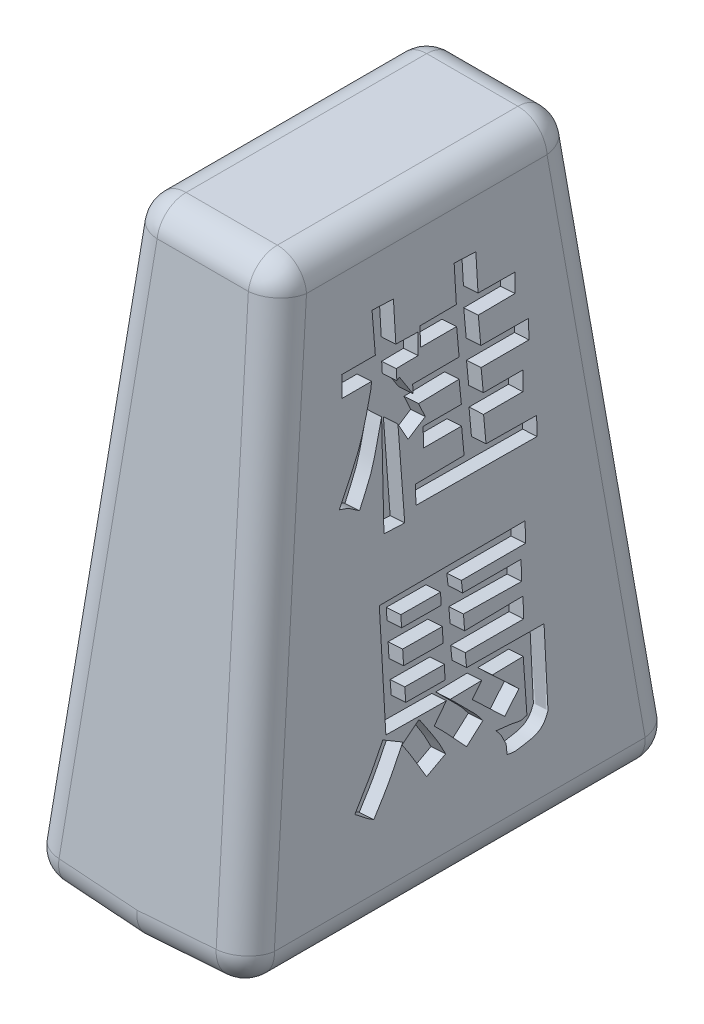
SolidWorks part; units mm, degrees
ref_plane "Płaszczyzna przednia" through (0, 0, 0) normal (0, 0, 1) x (1, 0, 0)
ref_plane "Płaszczyzna górna" through (0, 0, 0) normal (0, 1, 0) x (1, 0, 0)
ref_plane "Płaszczyzna prawa" through (0, 0, 0) normal (1, 0, 0) x (0, 0, -1)
sketch "Szkic1" plane through (0, 0, 0) normal (0, 0, 1) x (1, 0, 0)
  line L0 (0, 0) -> (0, 40)
  line L1 (3.1225, 40) -> (-3.1225, 40)
  line L2 (-5.1185, 38.1262) -> (-7.3738, 2.4704)
  line L3 (-5.504, 0.3481) -> (0, 0)
  line L4 (5.504, 0.3481) -> (0, 0)
  line L5 (5.1185, 38.1262) -> (7.3738, 2.4704)
  arc A0 (-3.1225, 40) -> (-5.1185, 38.1262) centre (-3.1225, 38) ccw
  arc A1 (-7.3738, 2.4704) -> (-5.504, 0.3481) centre (-5.3777, 2.3441) ccw
  arc A2 (7.3738, 2.4704) -> (5.504, 0.3481) centre (5.3777, 2.3441) cw
  arc A3 (3.1225, 40) -> (5.1185, 38.1262) centre (3.1225, 38) cw
  point P7 (-5, 40)
  point P10 (-7.5, 0.4744)
  point P17 (7.5, 0.4744)
  point P18 (5, 40)
  dimension "D5" = 2
  dimension "D1" = 40
  dimension "D2" = 90
  dimension "D3" = 5
  dimension "D4" = 7.5
extrude "Dodanie-wyciągnięcie1" add sketch "Szkic1" along normal blind 30 contours L2 A1 L3 L0 L1 A0 | A3 L1 L0 L4 A2 L5 region at (-3.1441, 18.7866, 0) region at (3.1441, 18.7866, 0)
ref_plane "Płaszczyzna1" through (5.1225, 0, 0) normal (1, 0, 0) x (0, 0, -1)
ref_plane "Płaszczyzna2" through (15.1225, 0, 0) normal (1, 0, 0) x (0, 0, -1)
sketch "Szkic7" plane through (15.1225, 0, 0) normal (1, 0, 0) x (0, 0, -1)
  line L0 (-25, 40) -> (-5, 40)
  line L1 (-30, 40) -> (0, 40) construction
  line L2 (-5, 40) -> (0, 0)
  line L3 (0, 0) -> (-30, 0)
  line L4 (-30, 0) -> (0, 0) construction
  line L5 (-15, 0) -> (-15, 40)
  line L6 (-25, 40) -> (-30, 0)
  line L8 (0, 0) -> (-30, 0)
  line L9 (0, 0) -> (0, 40)
  line L10 (0, 40) -> (-30, 40)
  line L11 (-30, 0) -> (-30, 40)
  dimension "D1" = 10
  dimension "D2" = 15
  dimension "D3" = 40
extrude "Wytnij-wyciągnięcie11" cut sketch "Szkic7" against normal through all and the other way through all contours L11 L6 L10 | L9 L10 L2 region at (15.1225, 26.6667, 28.3333) region at (15.1225, 26.6667, 1.6667)
fillet "Zaokrąglenie2" radius 2 18 edges at (0, 40, 5) (-4.4914, 39.4582, 4.9323) (-6.2461, 20.2983, 2.5373) (-6.8784, 1.022, 0.1278) (-2.752, 0.1741, 0.0218) (2.752, 0.1741, 0.0218) (6.8784, 1.022, 0.1278) (6.2461, 20.2983, 2.5373) (4.4914, 39.4582, 4.9323) (4.4914, 39.4582, 25.0677) (6.2461, 20.2983, 27.4627) (6.8784, 1.022, 29.8722) (2.752, 0.1741, 29.9782) (-2.752, 0.1741, 29.9782) (-6.8784, 1.022, 29.8722) (-6.2461, 20.2983, 27.4627) (-4.4914, 39.4582, 25.0677) (0, 40, 25)
sketch "Szkic8" plane through (7.5, 0.4744, 0) normal (0.998, 0.0631, 0) x (0, 0, -1)
  line L0 (341.3333, 1024) -> (1706.6667, 1024) construction
  line L1 (-18.9383, 34.682) -> (-17.4783, 34.622)
  line L2 (-17.4783, 34.622) -> (-17.4783, 32.022)
  line L3 (-17.4783, 32.022) -> (-15.9783, 31.982)
  line L4 (-15.9783, 31.982) -> (-16.0383, 30.662)
  line L5 (-16.0383, 30.662) -> (-17.5383, 30.642)
  line L6 (-17.5383, 30.642) -> (-17.5383, 29.942)
  line L7 (-17.5383, 29.942) -> (-17.3583, 30.062)
  line L8 (-17.3583, 30.062) -> (-16.5183, 28.702)
  line L9 (-16.5183, 28.702) -> (-16.4983, 29.242)
  line L10 (-16.4983, 29.242) -> (-13.3183, 29.262)
  line L11 (-13.3183, 29.262) -> (-13.3783, 31.042)
  line L12 (-13.3783, 31.042) -> (-15.8583, 31.042)
  line L13 (-15.8583, 31.042) -> (-15.7983, 32.262)
  line L14 (-15.7983, 32.262) -> (-13.3183, 32.282)
  line L15 (-13.3183, 32.282) -> (-13.3183, 34.662)
  line L16 (-13.3183, 34.662) -> (-11.8383, 34.602)
  line L17 (-11.8383, 34.602) -> (-11.8383, 32.222)
  line L18 (-11.8383, 32.222) -> (-9.3183, 32.202)
  line L19 (-9.3183, 32.202) -> (-9.3783, 31.002)
  line L20 (-9.3783, 31.002) -> (-11.8983, 30.982)
  line L21 (-11.8983, 30.982) -> (-11.8383, 29.202)
  line L22 (-11.8383, 29.202) -> (-8.5783, 29.182)
  line L23 (-8.5783, 29.182) -> (-8.6183, 27.962)
  line L24 (-8.6183, 27.962) -> (-11.8983, 27.962)
  line L25 (-11.8983, 27.962) -> (-11.8383, 26.482)
  line L26 (-11.8383, 26.482) -> (-9.1383, 26.482)
  line L27 (-9.1383, 26.482) -> (-9.1983, 25.262)
  line L28 (-9.1983, 25.262) -> (-11.8983, 25.262)
  line L29 (-11.8983, 25.262) -> (-11.8383, 23.542)
  line L30 (-11.8383, 23.542) -> (-8.3783, 23.502)
  line L31 (-8.3783, 23.502) -> (-8.4183, 22.302)
  line L32 (-8.4183, 22.302) -> (-16.7183, 22.362)
  line L33 (-16.7183, 22.362) -> (-16.6583, 23.562)
  line L34 (-16.6583, 23.562) -> (-13.3383, 23.602)
  line L35 (-13.3383, 23.602) -> (-13.3983, 25.322)
  line L36 (-13.3983, 25.322) -> (-15.9983, 25.322)
  line L37 (-15.9983, 25.322) -> (-15.9583, 26.542)
  line L38 (-15.9583, 26.542) -> (-13.3383, 26.542)
  line L39 (-13.3383, 26.542) -> (-13.3983, 28.022)
  line L40 (-13.3983, 28.022) -> (-16.1783, 27.962)
  line L41 (-16.1783, 27.962) -> (-15.7783, 27.022)
  line L42 (-15.7783, 27.022) -> (-16.9983, 26.302)
  line L43 (-16.9983, 26.302) -> (-17.6183, 27.482)
  line L44 (-17.6183, 27.482) -> (-17.5183, 21.742)
  line L45 (-17.5183, 21.742) -> (-18.9383, 21.802)
  line L46 (-18.9383, 21.802) -> (-18.6783, 28.422)
  line L47 (-19.2183, 30.722) -> (-21.2383, 30.722)
  line L48 (-21.2383, 30.722) -> (-21.1783, 32.062)
  line L49 (-21.1783, 32.062) -> (-18.8783, 32.062)
  line L50 (-18.8783, 32.062) -> (-18.9383, 34.682)
  line L51 (-9.5983, 18.002) -> (-9.5183, 17.962)
  line L52 (-9.5183, 17.962) -> (-9.5583, 16.702)
  line L53 (-9.5583, 16.702) -> (-13.9583, 16.702)
  line L54 (-13.9583, 16.702) -> (-13.9183, 15.962)
  line L55 (-13.9183, 15.962) -> (-9.9183, 15.962)
  line L56 (-9.9183, 15.962) -> (-9.9583, 14.702)
  line L57 (-9.9583, 14.702) -> (-13.9383, 14.762)
  line L58 (-13.9383, 14.762) -> (-13.9183, 13.782)
  line L59 (-13.9183, 13.782) -> (-9.9783, 13.842)
  line L60 (-9.9783, 13.842) -> (-9.9183, 13.802)
  line L61 (-9.9183, 13.802) -> (-9.9583, 12.542)
  line L62 (-9.9583, 12.542) -> (-13.9583, 12.542)
  line L63 (-13.9583, 12.542) -> (-13.9183, 11.662)
  line L64 (-13.9183, 11.662) -> (-8.6183, 11.622)
  line L65 (-10.0783, 7.062) -> (-10.1183, 10.462)
  line L66 (-10.1183, 10.462) -> (-12.2383, 10.422)
  line L67 (-12.2383, 10.422) -> (-10.5183, 8.802)
  line L68 (-10.5183, 8.802) -> (-11.5583, 7.702)
  line L69 (-11.5583, 7.702) -> (-13.6583, 9.702)
  line L70 (-13.6583, 9.702) -> (-12.9583, 10.462)
  line L71 (-12.9583, 10.462) -> (-15.1183, 10.422)
  line L72 (-13.0183, 8.182) -> (-14.1983, 7.242)
  line L73 (-16.2783, 9.442) -> (-15.3783, 10.462)
  line L74 (-15.3783, 10.462) -> (-19.5183, 10.502)
  line L75 (-19.5183, 10.502) -> (-19.4983, 17.942)
  line L76 (-19.4983, 17.942) -> (-9.5983, 17.982)
  line L77 (-9.5983, 17.982) -> (-9.5983, 18.002)
  line L78 (-18.0983, 16.742) -> (-15.3783, 16.722)
  line L79 (-15.3783, 16.722) -> (-15.3983, 15.962)
  line L80 (-15.3983, 15.962) -> (-18.0983, 15.982)
  line L81 (-18.0983, 15.982) -> (-18.0983, 16.742)
  line L82 (-18.0983, 14.762) -> (-15.3783, 14.742)
  line L83 (-15.3783, 14.742) -> (-15.3983, 13.782)
  line L84 (-15.3983, 13.782) -> (-18.0983, 13.802)
  line L85 (-18.0983, 13.802) -> (-18.0983, 14.762)
  line L86 (-18.0983, 12.582) -> (-15.3783, 12.562)
  line L87 (-15.3783, 12.562) -> (-15.3983, 11.662)
  line L88 (-15.3983, 11.662) -> (-18.0783, 11.682)
  line L89 (-18.0783, 11.682) -> (-18.0983, 12.582)
  line L90 (-15.6183, 7.522) -> (-16.9583, 6.862)
  line L91 (-18.4783, 9.422) -> (-17.2783, 10.282)
  line L92 (-19.7383, 10.322) -> (-18.4183, 9.562)
  line L93 (-9.5983, 18.002) -> (-9.5183, 17.962)
  line L94 (-9.5183, 17.962) -> (-9.5583, 16.702)
  line L95 (-9.5583, 16.702) -> (-13.9583, 16.702)
  line L96 (-13.9583, 16.702) -> (-13.9183, 15.962)
  line L97 (-13.9183, 15.962) -> (-9.9183, 15.962)
  line L98 (-9.9183, 15.962) -> (-9.9583, 14.702)
  line L99 (-9.9583, 14.702) -> (-13.9383, 14.762)
  line L100 (-13.9383, 14.762) -> (-13.9183, 13.782)
  line L101 (-13.9183, 13.782) -> (-9.9783, 13.842)
  line L102 (-9.9783, 13.842) -> (-9.9183, 13.802)
  line L103 (-9.9183, 13.802) -> (-9.9583, 12.542)
  line L104 (-9.9583, 12.542) -> (-13.9583, 12.542)
  line L105 (-13.9583, 12.542) -> (-13.9183, 11.662)
  line L106 (-13.9183, 11.662) -> (-8.6183, 11.622)
  line L107 (-10.0783, 7.062) -> (-10.1183, 10.462)
  line L108 (-10.1183, 10.462) -> (-12.2383, 10.422)
  line L109 (-12.2383, 10.422) -> (-10.5183, 8.802)
  line L110 (-10.5183, 8.802) -> (-11.5583, 7.702)
  line L111 (-11.5583, 7.702) -> (-13.6583, 9.702)
  line L112 (-13.6583, 9.702) -> (-12.9583, 10.462)
  line L113 (-12.9583, 10.462) -> (-15.1183, 10.422)
  line L114 (-13.0183, 8.182) -> (-14.1983, 7.242)
  line L115 (-16.2783, 9.442) -> (-15.3783, 10.462)
  line L116 (-15.3783, 10.462) -> (-19.5183, 10.502)
  line L117 (-19.5183, 10.502) -> (-19.4983, 17.942)
  line L118 (-19.4983, 17.942) -> (-9.5983, 17.982)
  line L119 (-9.5983, 17.982) -> (-9.5983, 18.002)
  line L120 (-18.0983, 16.742) -> (-15.3783, 16.722)
  line L121 (-15.3783, 16.722) -> (-15.3983, 15.962)
  line L122 (-15.3983, 15.962) -> (-18.0983, 15.982)
  line L123 (-18.0983, 15.982) -> (-18.0983, 16.742)
  line L124 (-18.0983, 14.762) -> (-15.3783, 14.742)
  line L125 (-15.3783, 14.742) -> (-15.3983, 13.782)
  line L126 (-15.3983, 13.782) -> (-18.0983, 13.802)
  line L127 (-18.0983, 13.802) -> (-18.0983, 14.762)
  line L128 (-18.0983, 12.582) -> (-15.3783, 12.562)
  line L129 (-15.3783, 12.562) -> (-15.3983, 11.662)
  line L130 (-15.3983, 11.662) -> (-18.0783, 11.682)
  line L131 (-18.0783, 11.682) -> (-18.0983, 12.582)
  line L132 (-9.5983, 18.002) -> (-9.5183, 17.962)
  line L133 (-9.5183, 17.962) -> (-9.5583, 16.702)
  line L134 (-9.5583, 16.702) -> (-13.9583, 16.702)
  line L135 (-13.9583, 16.702) -> (-13.9183, 15.962)
  line L136 (-13.9183, 15.962) -> (-9.9183, 15.962)
  line L137 (-9.9183, 15.962) -> (-9.9583, 14.702)
  line L138 (-9.9583, 14.702) -> (-13.9383, 14.762)
  line L139 (-13.9383, 14.762) -> (-13.9183, 13.782)
  line L140 (-13.9183, 13.782) -> (-9.9783, 13.842)
  line L141 (-9.9783, 13.842) -> (-9.9183, 13.802)
  line L142 (-9.9183, 13.802) -> (-9.9583, 12.542)
  line L143 (-9.9583, 12.542) -> (-13.9583, 12.542)
  line L144 (-13.9583, 12.542) -> (-13.9183, 11.662)
  line L145 (-13.9183, 11.662) -> (-8.6183, 11.622)
  line L146 (-10.0783, 7.062) -> (-10.1183, 10.462)
  line L147 (-10.1183, 10.462) -> (-12.2383, 10.422)
  line L148 (-12.2383, 10.422) -> (-10.5183, 8.802)
  line L149 (-10.5183, 8.802) -> (-11.5583, 7.702)
  line L150 (-11.5583, 7.702) -> (-13.6583, 9.702)
  line L151 (-13.6583, 9.702) -> (-12.9583, 10.462)
  line L152 (-12.9583, 10.462) -> (-15.1183, 10.422)
  line L153 (-13.0183, 8.182) -> (-14.1983, 7.242)
  line L154 (-16.2783, 9.442) -> (-15.3783, 10.462)
  line L155 (-15.3783, 10.462) -> (-19.5183, 10.502)
  line L156 (-19.5183, 10.502) -> (-19.4983, 17.942)
  line L157 (-19.4983, 17.942) -> (-9.5983, 17.982)
  line L158 (-9.5983, 17.982) -> (-9.5983, 18.002)
  line L159 (-18.0983, 16.742) -> (-15.3783, 16.722)
  line L160 (-15.3783, 16.722) -> (-15.3983, 15.962)
  line L161 (-15.3983, 15.962) -> (-18.0983, 15.982)
  line L162 (-18.0983, 15.982) -> (-18.0983, 16.742)
  line L163 (-18.0983, 14.762) -> (-15.3783, 14.742)
  line L164 (-15.3783, 14.742) -> (-15.3983, 13.782)
  line L165 (-15.3983, 13.782) -> (-18.0983, 13.802)
  line L166 (-18.0983, 13.802) -> (-18.0983, 14.762)
  line L167 (-18.0983, 12.582) -> (-15.3783, 12.562)
  line L168 (-15.3783, 12.562) -> (-15.3983, 11.662)
  line L169 (-15.3983, 11.662) -> (-18.0783, 11.682)
  line L170 (-18.0783, 11.682) -> (-18.0983, 12.582)
  spline S0 degree 3 poles (-18.6783, 28.422) (-18.6849, 28.402) (-18.6919, 28.3821) (-18.6983, 28.362) (-18.9719, 27.5021) (-19.1851, 26.6206) (-19.5183, 25.782) (-19.7803, 25.1226) (-20.1583, 24.5154) (-20.4783, 23.882) knots 0 0 0 0 1 1 1 2 2 2 3 3 3 3
  spline S1 degree 3 poles (-20.4783, 23.882) (-20.7183, 24.042) (-20.9426, 24.2285) (-21.1983, 24.362) (-21.3926, 24.4636) (-21.6116, 24.5087) (-21.8183, 24.582) knots 0 0 0 0 1 1 1 2 2 2 2
  spline S2 degree 3 poles (-21.8183, 24.582) (-21.3049, 25.5287) (-20.7193, 26.4396) (-20.2783, 27.422) (-19.8966, 28.2722) (-19.6433, 29.1748) (-19.3583, 30.062) (-19.2895, 30.2761) (-19.2649, 30.502) (-19.2183, 30.722) knots 0 0 0 0 1 1 1 2 2 2 3 3 3 3
  spline S3 degree 3 poles (-8.6183, 11.622) (-8.6316, 9.962) (-8.6384, 8.302) (-8.6583, 6.642) (-8.6585, 6.6271) (-8.671, 6.615) (-8.6783, 6.602) (-8.7643, 6.4484) (-8.8258, 6.2776) (-8.9383, 6.142) (-9.056, 6.0001) (-9.1945, 5.8668) (-9.3583, 5.782) (-9.5755, 5.6696) (-9.8168, 5.601) (-10.0583, 5.562) (-11.0949, 5.3945) (-10.9681, 5.388) (-11.5383, 5.502) knots 0 0 0 0 1 1 1 2 2 2 3 3 3 4 4 4 5 5 5 6 6 6 6
  spline S4 degree 3 poles (-11.5383, 5.502) (-11.5449, 5.7087) (-11.5458, 5.9156) (-11.5583, 6.122) (-11.5592, 6.1369) (-11.5718, 6.1486) (-11.5783, 6.162) (-11.6718, 6.3553) (-11.7494, 6.557) (-11.8583, 6.742) (-11.9502, 6.8983) (-12.0716, 7.0354) (-12.1783, 7.182) knots 0 0 0 0 1 1 1 2 2 2 3 3 3 4 4 4 4
  spline S5 degree 3 poles (-12.1783, 7.182) (-10.1699, 7.0181) (-10.8486, 6.8419) (-10.0783, 7.062) knots 0 0 0 0 1 1 1 1
  spline S6 degree 3 poles (-15.1183, 10.422) (-14.5783, 9.8754) (-14.0238, 9.3426) (-13.4983, 8.782) (-13.3231, 8.5952) (-13.1783, 8.382) (-13.0183, 8.182) knots 0 0 0 0 1 1 1 2 2 2 2
  spline S7 degree 3 poles (-14.1983, 7.242) (-14.6849, 7.7687) (-15.1656, 8.301) (-15.6583, 8.822) (-15.8591, 9.0344) (-16.0716, 9.2354) (-16.2783, 9.442) knots 0 0 0 0 1 1 1 2 2 2 2
  spline S8 degree 3 poles (-17.2783, 10.282) (-17.2449, 10.2487) (-17.2041, 10.2215) (-17.1783, 10.182) (-16.8235, 9.6406) (-16.4657, 9.1004) (-16.1383, 8.542) (-15.9452, 8.2128) (-15.7916, 7.862) (-15.6183, 7.522) knots 0 0 0 0 1 1 1 2 2 2 3 3 3 3
  spline S9 degree 3 poles (-16.9583, 6.862) (-17.3116, 7.4754) (-17.6569, 8.0934) (-18.0183, 8.702) (-18.1637, 8.9469) (-18.3249, 9.182) (-18.4783, 9.422) knots 0 0 0 0 1 1 1 2 2 2 2
  spline S10 degree 3 poles (-18.4183, 9.562) (-18.7983, 8.9287) (-19.157, 8.2821) (-19.5583, 7.662) (-19.8909, 7.148) (-20.2649, 6.662) (-20.6183, 6.162) knots 0 0 0 0 1 1 1 2 2 2 2
  spline S11 degree 3 poles (-20.6183, 6.162) (-20.7449, 6.242) (-20.877, 6.314) (-20.9983, 6.402) (-21.2907, 6.6143) (-21.5716, 6.842) (-21.8583, 7.062) knots 0 0 0 0 1 1 1 2 2 2 2
  spline S12 degree 3 poles (-21.8583, 7.062) (-21.4449, 7.662) (-21.0155, 8.2512) (-20.6183, 8.862) (-20.3085, 9.3384) (-20.0316, 9.8354) (-19.7383, 10.322) knots 0 0 0 0 1 1 1 2 2 2 2
  spline S13 degree 3 poles (-8.6183, 11.622) (-8.6316, 9.962) (-8.6384, 8.302) (-8.6583, 6.642) (-8.6585, 6.6271) (-8.671, 6.615) (-8.6783, 6.602) (-8.7643, 6.4484) (-8.8258, 6.2776) (-8.9383, 6.142) (-9.056, 6.0001) (-9.1945, 5.8668) (-9.3583, 5.782) (-9.5755, 5.6696) (-9.8168, 5.601) (-10.0583, 5.562) (-11.0949, 5.3945) (-10.9681, 5.388) (-11.5383, 5.502) knots 0 0 0 0 1 1 1 2 2 2 3 3 3 4 4 4 5 5 5 6 6 6 6
  spline S14 degree 3 poles (-11.5383, 5.502) (-11.5449, 5.7087) (-11.5458, 5.9156) (-11.5583, 6.122) (-11.5592, 6.1369) (-11.5718, 6.1486) (-11.5783, 6.162) (-11.6718, 6.3553) (-11.7494, 6.557) (-11.8583, 6.742) (-11.9502, 6.8983) (-12.0716, 7.0354) (-12.1783, 7.182) knots 0 0 0 0 1 1 1 2 2 2 3 3 3 4 4 4 4
  spline S15 degree 3 poles (-12.1783, 7.182) (-10.1699, 7.0181) (-10.8486, 6.8419) (-10.0783, 7.062) knots 0 0 0 0 1 1 1 1
  spline S16 degree 3 poles (-15.1183, 10.422) (-14.5783, 9.8754) (-14.0238, 9.3426) (-13.4983, 8.782) (-13.3231, 8.5952) (-13.1783, 8.382) (-13.0183, 8.182) knots 0 0 0 0 1 1 1 2 2 2 2
  spline S17 degree 3 poles (-14.1983, 7.242) (-14.6849, 7.7687) (-15.1656, 8.301) (-15.6583, 8.822) (-15.8591, 9.0344) (-16.0716, 9.2354) (-16.2783, 9.442) knots 0 0 0 0 1 1 1 2 2 2 2
  spline S18 degree 3 poles (-8.6183, 11.622) (-8.6316, 9.962) (-8.6384, 8.302) (-8.6583, 6.642) (-8.6585, 6.6271) (-8.671, 6.615) (-8.6783, 6.602) (-8.7643, 6.4484) (-8.8258, 6.2776) (-8.9383, 6.142) (-9.056, 6.0001) (-9.1945, 5.8668) (-9.3583, 5.782) (-9.5755, 5.6696) (-9.8168, 5.601) (-10.0583, 5.562) (-11.0949, 5.3945) (-10.9681, 5.388) (-11.5383, 5.502) knots 0 0 0 0 1 1 1 2 2 2 3 3 3 4 4 4 5 5 5 6 6 6 6
  spline S19 degree 3 poles (-11.5383, 5.502) (-11.5449, 5.7087) (-11.5458, 5.9156) (-11.5583, 6.122) (-11.5592, 6.1369) (-11.5718, 6.1486) (-11.5783, 6.162) (-11.6718, 6.3553) (-11.7494, 6.557) (-11.8583, 6.742) (-11.9502, 6.8983) (-12.0716, 7.0354) (-12.1783, 7.182) knots 0 0 0 0 1 1 1 2 2 2 3 3 3 4 4 4 4
  spline S20 degree 3 poles (-12.1783, 7.182) (-10.1699, 7.0181) (-10.8486, 6.8419) (-10.0783, 7.062) knots 0 0 0 0 1 1 1 1
  spline S21 degree 3 poles (-15.1183, 10.422) (-14.5783, 9.8754) (-14.0238, 9.3426) (-13.4983, 8.782) (-13.3231, 8.5952) (-13.1783, 8.382) (-13.0183, 8.182) knots 0 0 0 0 1 1 1 2 2 2 2
  spline S22 degree 3 poles (-14.1983, 7.242) (-14.6849, 7.7687) (-15.1656, 8.301) (-15.6583, 8.822) (-15.8591, 9.0344) (-16.0716, 9.2354) (-16.2783, 9.442) knots 0 0 0 0 1 1 1 2 2 2 2
extrude "Wytnij-wyciągnięcie12" cut sketch "Szkic8" against normal blind 1 contours S2 S1 S0 L46 L45 L44 L43 L42 L41 L40 L39 L38 L37 L36 L35 L34 L33 L32 L31 L30 L29 L28 L27 L26 L25 L24 L23 L22 L21 L20 L19 L18 L17 L16 L15 L14 L13 L12 L11 L10 L9 L8 L7 L6 L5 L4 L3 L2 L1 L50 L49 | S7 L72 S6 L71 L70 L69 L68 L67 L66 L65 S5 S4 S3 L64 L63 L62 L61 L60 L59 L58 L57 L56 L55 L54 L53 L52 L51 L77 L76 L75 L74 L73 L80 L81 L78 L79 L84 L85 L82 L83 L88 L89 L86 L87 | S9 L90 S8 L91 | S12 S11 S10 L92 region at (5.3244, 34.8713, 18.2159) region at (6.7038, 13.0622, 13.995) region at (6.9582, 9.0411, 17.066) region at (6.9797, 8.7, 20.1286)
sketch "Szkic9" plane through (-7.5, 0.4744, 0) normal (-0.998, 0.0631, 0) x (0, 0, 1)
  line L0 (341.3333, 1024) -> (1706.6667, 1024) construction
  line L14 (16.0268, 22.7527) -> (16.6028, 23.9047)
  line L19 (14.5868, 13.1847) -> (7.7068, 13.2327)
  line L20 (17.3708, 10.9767) -> (13.8828, 5.2327)
  line L21 (13.8828, 5.2327) -> (15.9308, 3.9847)
  line L22 (15.9308, 3.9847) -> (21.5468, 13.1847)
  line L23 (21.5468, 13.1847) -> (15.4988, 13.2167)
  line L24 (15.4988, 13.2167) -> (16.9868, 14.2567)
  line L25 (13.4668, 18.5927) -> (13.1788, 18.3367)
  line L26 (4.8268, 13.6007) -> (5.0188, 15.0087)
  line L27 (24.8588, 14.7367) -> (24.7308, 15.5367)
  spline S0 degree 3 poles (24.7308, 15.5367) (24.0748, 15.8353) (23.4041, 16.1036) (22.7628, 16.4327) (22.1866, 16.7283) (21.6281, 17.0592) (21.0828, 17.4087) (20.6616, 17.6786) (20.2565, 17.9748) (19.8668, 18.2887) (19.4608, 18.6156) (19.0674, 18.96) (18.6988, 19.3287) (18.3408, 19.6866) (18.0089, 20.0708) (17.6908, 20.4647) (17.203, 21.0688) (16.7396, 21.6926) (16.2828, 22.3207) (16.1844, 22.456) (16.1122, 22.6087) (16.0268, 22.7527) knots 0 0 0 0 1 1 1 2 2 2 3 3 3 4 4 4 5 5 5 6 6 6 7 7 7 7
  spline S1 degree 3 poles (16.6028, 23.9047) (16.1495, 24.0967) (15.6877, 24.2699) (15.2428, 24.4807) (14.8762, 24.6543) (14.5282, 24.8647) (14.1708, 25.0567) knots 0 0 0 0 1 1 1 2 2 2 2
  spline S2 degree 3 poles (14.1708, 25.0567) (13.8295, 24.342) (13.5096, 23.6167) (13.1468, 22.9127) (12.7946, 22.2293) (12.4203, 21.5571) (12.0268, 20.8967) (11.8065, 20.5269) (11.568, 20.1668) (11.3068, 19.8247) (11.0337, 19.4669) (10.7386, 19.1252) (10.4268, 18.8007) (10.087, 18.4469) (9.728, 18.111) (9.3548, 17.7927) (8.9644, 17.4596) (8.5572, 17.1457) (8.1388, 16.8487) (7.6925, 16.5318) (7.2343, 16.2307) (6.7628, 15.9527) (6.1934, 15.6169) (5.6002, 15.3233) (5.0188, 15.0087) knots 0 0 0 0 1 1 1 2 2 2 3 3 3 4 4 4 5 5 5 6 6 6 7 7 7 8 8 8 8
  spline S3 degree 3 poles (14.7468, 20.5767) (15.0668, 20.1553) (15.3659, 19.7172) (15.7068, 19.3127) (16.1666, 18.767) (16.6476, 18.2385) (17.1468, 17.7287) (17.6562, 17.2085) (18.1839, 16.7052) (18.7308, 16.2247) (19.1075, 15.8937) (19.5056, 15.5864) (19.9148, 15.2967) (20.3652, 14.9778) (20.8307, 14.6795) (21.3068, 14.4007) (21.7968, 14.1137) (22.3016, 13.8519) (22.8108, 13.6007) (23.1022, 13.4569) (23.4082, 13.3447) (23.7068, 13.2167) knots 0 0 0 0 1 1 1 2 2 2 3 3 3 4 4 4 5 5 5 6 6 6 7 7 7 7
  spline S4 degree 3 poles (23.7068, 13.2167) (23.7175, 13.238) (23.7276, 13.2596) (23.7388, 13.2807) (23.861, 13.5103) (23.9573, 13.7558) (24.1068, 13.9687) (24.2741, 14.2068) (24.4792, 14.4167) (24.6828, 14.6247) (24.7315, 14.6744) (24.8002, 14.6993) (24.8588, 14.7367) knots 0 0 0 0 1 1 1 2 2 2 3 3 3 4 4 4 4
  spline S5 degree 3 poles (4.8268, 13.6007) (4.9602, 13.3927) (5.1112, 13.195) (5.2268, 12.9767) (5.352, 12.7402) (5.4402, 12.486) (5.5468, 12.2407) knots 0 0 0 0 1 1 1 2 2 2 2
  spline S6 degree 3 poles (5.5468, 12.2407) (6.1815, 12.582) (6.8306, 12.8978) (7.4508, 13.2647) (7.9677, 13.5704) (8.4709, 13.9009) (8.9548, 14.2567) (9.4588, 14.6272) (9.9399, 15.0289) (10.4108, 15.4407) (10.8738, 15.8455) (11.3068, 16.2833) (11.7548, 16.7047) knots 0 0 0 0 1 1 1 2 2 2 3 3 3 4 4 4 4
  spline S7 degree 3 poles (11.7548, 16.7047) (12.1815, 16.2193) (12.6248, 15.7481) (13.0348, 15.2487) (13.581, 14.5833) (14.1272, 13.9125) (14.5868, 13.1847) knots 0 0 0 0 1 1 1 2 2 2 2
  spline S8 degree 3 poles (7.7068, 13.2327) (7.7228, 12.7687) (7.7516, 12.3049) (7.7548, 11.8407) (7.7569, 11.5365) (7.7335, 11.2327) (7.7228, 10.9287) knots 0 0 0 0 1 1 1 2 2 2 2
  spline S9 degree 3 poles (7.7228, 10.9287) (8.9495, 10.9553) (10.1759, 11.0026) (11.4028, 11.0087) (13.3922, 11.0186) (15.3815, 10.9873) (17.3708, 10.9767) knots 0 0 0 0 1 1 1 2 2 2 2
  spline S10 degree 3 poles (16.9868, 14.2567) (16.5708, 14.8273) (16.1734, 15.412) (15.7388, 15.9687) (15.261, 16.5806) (14.759, 17.1737) (14.2508, 17.7607) (14.0014, 18.0487) (13.7282, 18.3153) (13.4668, 18.5927) knots 0 0 0 0 1 1 1 2 2 2 3 3 3 3
  spline S11 degree 3 poles (13.1788, 18.3367) (13.5415, 18.8327) (13.9145, 19.3213) (14.2668, 19.8247) (14.4374, 20.0683) (14.5868, 20.326) (14.7468, 20.5767) knots 0 0 0 0 1 1 1 2 2 2 2
extrude "Wytnij-wyciągnięcie13" cut sketch "Szkic9" against normal blind 1 contours L25 S11 S3 S4 L27 S0 L14 S1 S2 L26 S5 S6 S7 L19 S8 S9 L20 L21 L22 L23 L24 S10 region at (-6.5571, 15.3815, 14.7444)
